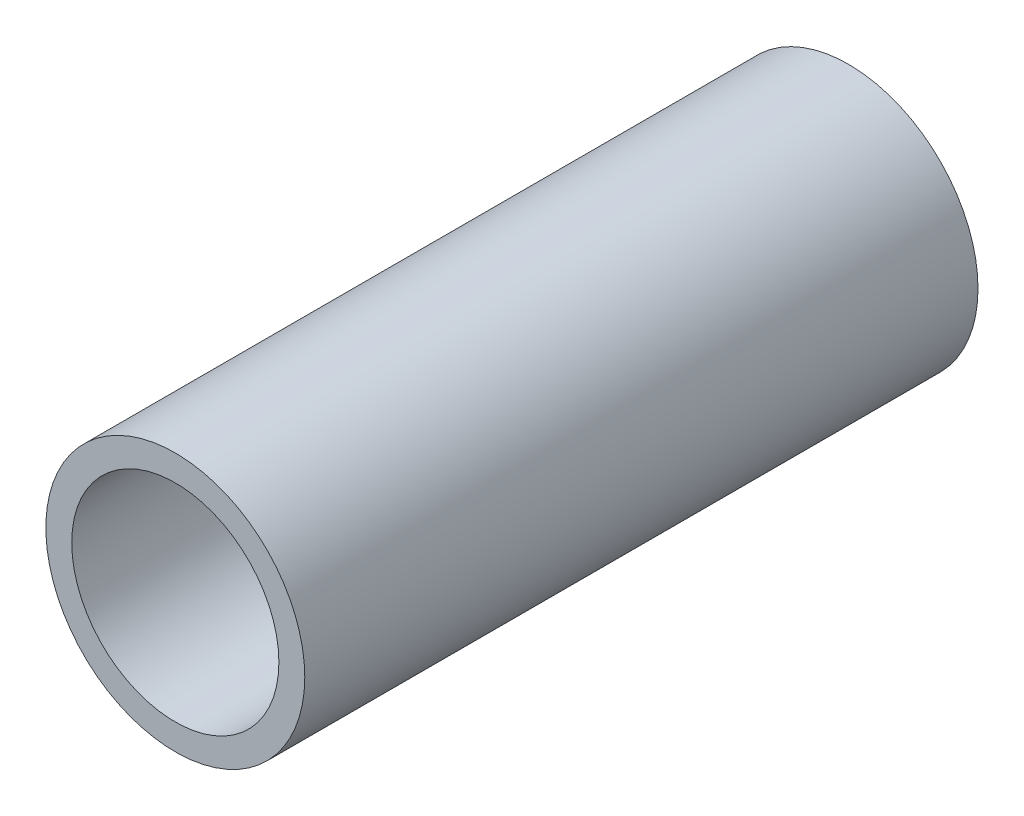
SolidWorks part; units mm, degrees
material "Nylon 101"
ref_plane "Front Plane" through (0, 0, 0) normal (0, 0, 1) x (1, 0, 0)
ref_plane "Top Plane" through (0, 0, 0) normal (0, 1, 0) x (1, 0, 0)
ref_plane "Right Plane" through (0, 0, 0) normal (1, 0, 0) x (0, 0, -1)
sketch "Sketch1" plane through (0, 0, 0) normal (0, 0, 1) x (1, 0, 0)
  circle A0 centre (0, 0) radius 6.35
  circle A1 centre (0, 0) radius 7.9375
  dimension "D1" = 12.7
  dimension "D2" = 15.875
extrude "Boss-Extrude1" add sketch "Sketch1" along normal mid plane 41.275
